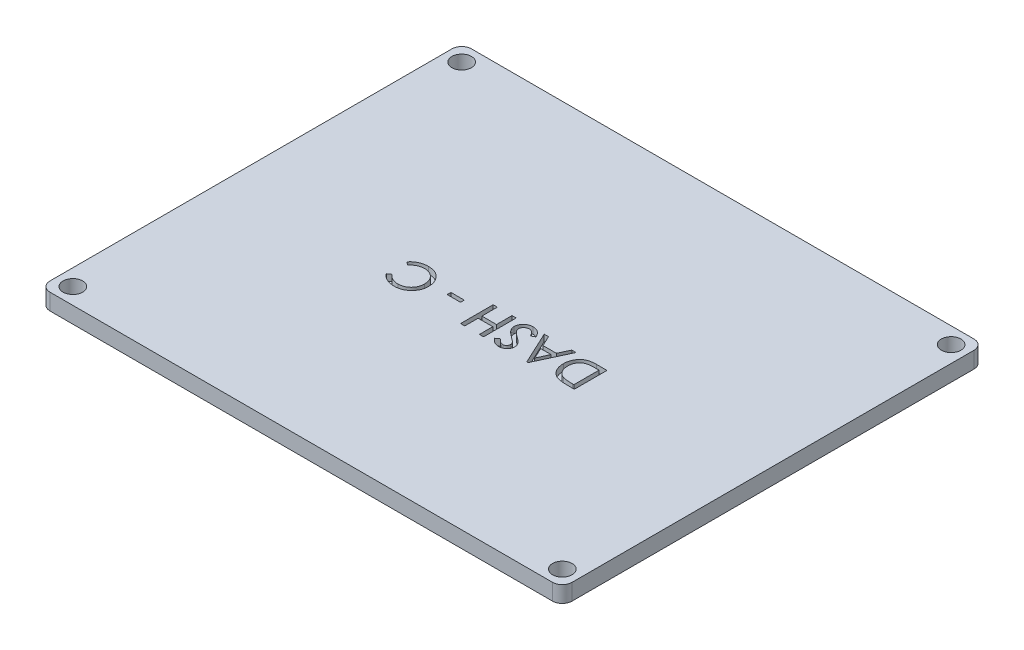
SolidWorks part; units mm, degrees
ref_plane "Front Plane" through (0, 0, 0) normal (0, 0, 1) x (1, 0, 0)
ref_plane "Top Plane" through (0, 0, 0) normal (0, 1, 0) x (1, 0, 0)
ref_plane "Right Plane" through (0, 0, 0) normal (1, 0, 0) x (0, 0, -1)
sketch "Sketch4" plane through (0, 0, 0) normal (0, 1, 0) x (1, 0, 0)
  line L5 (5.2791, -38.8005) -> (5.2791, 22.7841) construction
  line L6 (3.7791, -40.3005) -> (-73.2209, -40.3005) construction
  line L7 (-74.7209, -38.8005) -> (-74.7209, 22.7841) construction
  line L8 (3.7791, 24.2841) -> (-73.2209, 24.2841) construction
  line L9 (5.2791, -38.8005) -> (5.2791, 22.7841)
  line L10 (3.7791, -40.3005) -> (-73.2209, -40.3005)
  line L11 (-74.7209, -38.8005) -> (-74.7209, 22.7841)
  line L12 (3.7791, 24.2841) -> (-73.2209, 24.2841)
  line L17 (-23.2784, 15.2841) -> (-23.2784, 21.7841)
  line L18 (-23.2784, 15.2841) -> (-1.6485, 15.2841)
  line L19 (-1.6485, 15.2841) -> (-1.6485, 21.7841)
  line L21 (2.7791, -33.5578) -> (2.7791, 17.5415)
  line L22 (-67.9782, -37.8005) -> (-1.4635, -37.8005)
  line L23 (-72.2209, 17.5415) -> (-72.2209, -33.5578)
  line L24 (-1.4635, 21.7841) -> (-67.9782, 21.7841)
  line L25 (2.7791, -33.5578) -> (2.7791, 17.5415)
  line L26 (-67.9782, -37.8005) -> (-1.4635, -37.8005)
  line L27 (-72.2209, 17.5415) -> (-72.2209, -33.5578)
  line L28 (-1.4635, 21.7841) -> (-67.9782, 21.7841)
  circle A1 centre (2.7791, 21.7841) radius 1.5 construction
  circle A2 centre (-72.2209, 21.7841) radius 1.5
  circle A3 centre (-72.2209, 21.7841) radius 1.5
  arc A4 (5.2791, 22.7841) -> (3.7791, 24.2841) centre (3.7791, 22.7841) ccw construction
  circle A5 centre (2.7791, -37.8005) radius 1.5 construction
  arc A6 (3.7791, -40.3005) -> (5.2791, -38.8005) centre (3.7791, -38.8005) ccw construction
  arc A7 (-74.7209, -38.8005) -> (-73.2209, -40.3005) centre (-73.2209, -38.8005) ccw construction
  circle A8 centre (-72.2209, -37.8005) radius 1.5 construction
  arc A9 (-73.2209, 24.2841) -> (-74.7209, 22.7841) centre (-73.2209, 22.7841) ccw construction
  circle A10 centre (2.7791, 21.7841) radius 1.5
  arc A11 (5.2791, 22.7841) -> (3.7791, 24.2841) centre (3.7791, 22.7841) ccw
  circle A12 centre (2.7791, -37.8005) radius 1.5
  arc A13 (3.7791, -40.3005) -> (5.2791, -38.8005) centre (3.7791, -38.8005) ccw
  arc A14 (-74.7209, -38.8005) -> (-73.2209, -40.3005) centre (-73.2209, -38.8005) ccw
  circle A15 centre (-72.2209, -37.8005) radius 1.5
  arc A16 (-73.2209, 24.2841) -> (-74.7209, 22.7841) centre (-73.2209, 22.7841) ccw
  arc A41 (-0.0493, 20.7841) -> (-1.4635, 21.7841) centre (-1.4635, 20.2841) ccw
  arc A42 (-0.0493, 20.7841) -> (1.7791, 18.9557) centre (2.7791, 21.7841) ccw
  arc A43 (2.7791, 17.5415) -> (1.7791, 18.9557) centre (1.2791, 17.5415) ccw
  arc A44 (1.7791, -34.972) -> (2.7791, -33.5578) centre (1.2791, -33.5578) ccw
  arc A45 (1.7791, -34.972) -> (-0.0493, -36.8005) centre (2.7791, -37.8005) ccw
  arc A46 (-1.4635, -37.8005) -> (-0.0493, -36.8005) centre (-1.4635, -36.3005) ccw
  arc A47 (-69.3924, -36.8005) -> (-67.9782, -37.8005) centre (-67.9782, -36.3005) ccw
  arc A48 (-69.3924, -36.8005) -> (-71.2209, -34.972) centre (-72.2209, -37.8005) ccw
  arc A49 (-72.2209, -33.5578) -> (-71.2209, -34.972) centre (-70.7209, -33.5578) ccw
  arc A50 (-71.2209, 18.9557) -> (-72.2209, 17.5415) centre (-70.7209, 17.5415) ccw
  arc A51 (-71.2209, 18.9557) -> (-69.3924, 20.7841) centre (-72.2209, 21.7841) ccw
  arc A52 (-67.9782, 21.7841) -> (-69.3924, 20.7841) centre (-67.9782, 20.2841) ccw
  arc A53 (-0.0493, 20.7841) -> (-1.4635, 21.7841) centre (-1.4635, 20.2841) ccw
  arc A54 (-0.0493, 20.7841) -> (1.7791, 18.9557) centre (2.7791, 21.7841) ccw
  arc A55 (2.7791, 17.5415) -> (1.7791, 18.9557) centre (1.2791, 17.5415) ccw
  arc A56 (1.7791, -34.972) -> (2.7791, -33.5578) centre (1.2791, -33.5578) ccw
  arc A57 (1.7791, -34.972) -> (-0.0493, -36.8005) centre (2.7791, -37.8005) ccw
  arc A58 (-1.4635, -37.8005) -> (-0.0493, -36.8005) centre (-1.4635, -36.3005) ccw
  arc A59 (-69.3924, -36.8005) -> (-67.9782, -37.8005) centre (-67.9782, -36.3005) ccw
  arc A60 (-69.3924, -36.8005) -> (-71.2209, -34.972) centre (-72.2209, -37.8005) ccw
  arc A61 (-72.2209, -33.5578) -> (-71.2209, -34.972) centre (-70.7209, -33.5578) ccw
  arc A62 (-71.2209, 18.9557) -> (-72.2209, 17.5415) centre (-70.7209, 17.5415) ccw
  arc A63 (-71.2209, 18.9557) -> (-69.3924, 20.7841) centre (-72.2209, 21.7841) ccw
  arc A64 (-67.9782, 21.7841) -> (-69.3924, 20.7841) centre (-67.9782, 20.2841) ccw
  dimension "D1" = 0
  dimension "D2" = 0.5
extrude "BASE" add sketch "Sketch4" along normal blind 2.5 contours L28 A64 A63 A62 L27 A61 A60 A59 L26 A58 A57 A56 L25 A55 A54 A53 L19 L18 L17 | L12 A16 L11 A14 L10 A13 L9 A11 A64 L28 A53 A54 A55 L25 A56 A57 A58 L26 A59 A60 A61 L27 A62 A63 A3 A10 A12 A15 | L19 L28 L17 L18 region at (4.1128, 0, 39.1341) region at (-35.449, 0, 8.8764) region at (-12.4635, 0, -18.5341)
extrude "Boss-Extrude4" add sketch "Sketch4<3>" against normal blind 1 from surface contours L28 A64 A63 A62 L27 A61 A60 A59 L26 A58 A57 A56 L25 A55 A54 A53 L19 L18 L17 region at (-35.449, 0, 8.8764) starting at face at (-72.2209, 0, -20.2841)
sketch "Sketch4<3>" plane through (0, 0, 0) normal (0, 1, 0) x (1, 0, 0) same geometry as "Sketch4"
sketch "Sketch5" plane through (0, 2.5, 0) normal (0, 1, 0) x (1, 0, 0)
  line L0 (5.2791, -8.0082) -> (-74.7209, -8.0082) construction
  line L1 (5.2791, -38.8005) -> (5.2791, 22.7841) construction
  line L2 (-74.7209, -38.8005) -> (-74.7209, 22.7841) construction
  text T0 "<b>DASH - C</b>" font "Century Gothic" height 5
extrude "Cut-Extrude2" cut sketch "Sketch5" against normal blind 1
